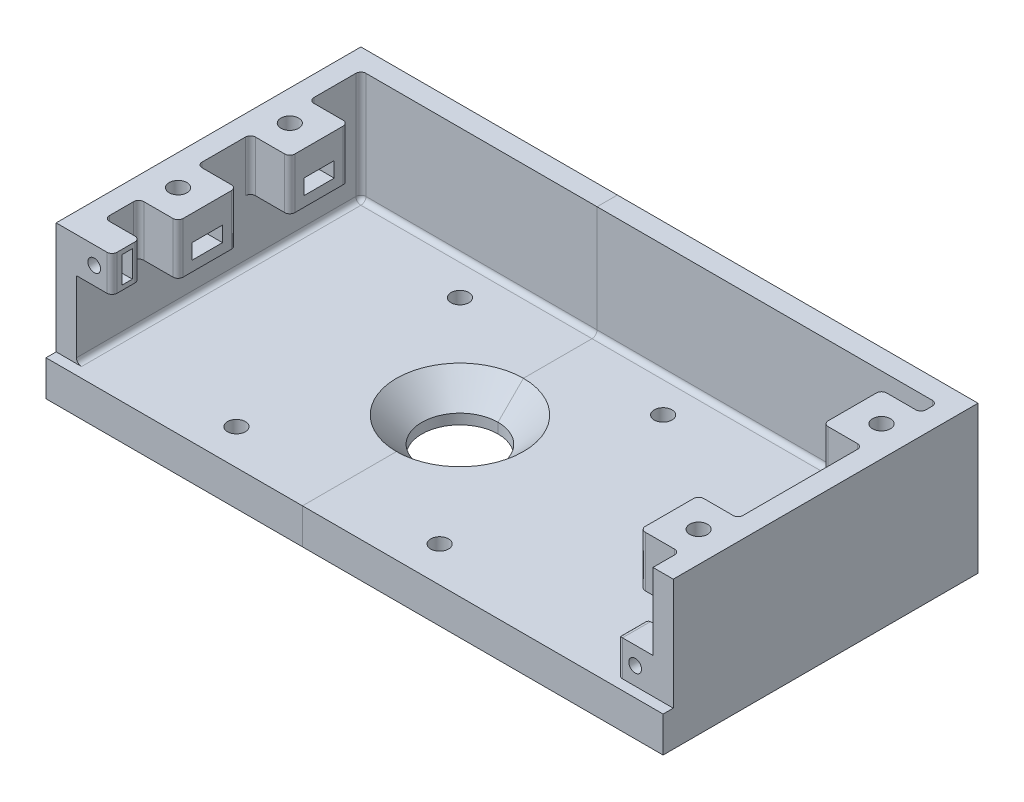
SolidWorks part; units mm, degrees
ref_plane "Front Plane" through (0, 0, 0) normal (0, 0, 1) x (1, 0, 0)
ref_plane "Top Plane" through (0, 0, 0) normal (0, 1, 0) x (1, 0, 0)
ref_plane "Right Plane" through (0, 0, 0) normal (1, 0, 0) x (0, 0, -1)
sketch "Sketch1" plane through (0, 0, 0) normal (0, 1, 0) x (1, 0, 0)
  line L0 (-50.5, 0) -> (71, 0) construction
  line L1 (-50.5, 31) -> (71, 31)
  line L2 (-50.5, 31) -> (-50.5, -31)
  line L3 (-50.5, -31) -> (71, -31)
  line L4 (71, 31) -> (71, -31)
  dimension "D1" = 121.5
  dimension "D2" = 62
  dimension "D3" = 71
extrude "Boss-Extrude1" add sketch "Sketch1" along normal blind 7
hole_wizard "CSK for M10 Flat Head Machine Screw1" positions "Sketch2" profile "Sketch3" countersink size "M10" standard "ANSI Metric" end condition through all
sketch "Sketch2" plane through (0, 7, 0) normal (0, 1, 0) x (1, 0, 0)
  point P0 (0, 0)
sketch "Sketch3" plane through (0, 7, 0) normal (1, 0, 0) x (0, 0, 1)
  line L0 (0, 0) -> (0, 7)
  line L1 (0, 7) -> (7.5, 7)
  line L2 (7.5, 7) -> (7.5, 5)
  line L3 (7.5, 5) -> (12.5, 0)
  line L5 (12.5, 0) -> (0, 0)
  line L6 (-7.5, 5) -> (-12.5, 0) construction
  line L11 (0, -6.35) -> (0, 107.95) construction
  dimension "Thru Hole Dia." = 15
  dimension "Thru Hole Depth" = 7
  dimension "Near C'Sink Dia." = 25
  dimension "Near C'Sink Angle" = 90
sketch "Sketch4" plane through (0, 7, 0) normal (0, 1, 0) x (1, 0, 0)
  line L8 (-50.5, 31) -> (-50.5, -29)
  line L9 (-50.5, 31) -> (-50.5, -31) construction
  line L10 (-50.5, -29) -> (-46.5, -29)
  line L11 (-46.5, -29) -> (-46.5, 27)
  line L12 (-46.5, 27) -> (67, 27)
  line L13 (67, 27) -> (67, -29)
  line L14 (67, -29) -> (71, -29)
  line L15 (71, -31) -> (71, 31) construction
  line L16 (71, -29) -> (71, 31)
  line L17 (71, 31) -> (-50.5, 31)
  line L18 (-50.5, -31) -> (71, -31) construction
  dimension "D1" = 2
  dimension "D2" = 4
  dimension "D3" = 4
extrude "Boss-Extrude2" add sketch "Sketch4" along normal blind 22
sketch "Sketch5" plane through (0, 29, 0) normal (0, 1, 0) x (1, 0, 0)
  line L1 (-50.25, 16.75) -> (-38.75, 16.75)
  line L2 (-50.25, 16.75) -> (-50.25, 5.25)
  line L3 (-50.25, 5.25) -> (-38.75, 5.25)
  line L4 (-38.75, 16.75) -> (-38.75, 5.25)
  line L5 (-50.25, 16.75) -> (-38.75, 5.25) construction
  line L6 (-50.25, 5.25) -> (-38.75, 16.75) construction
  line L7 (-50.25, -5.25) -> (-38.75, -5.25)
  line L8 (-50.25, -5.25) -> (-50.25, -16.75)
  line L9 (-50.25, -16.75) -> (-38.75, -16.75)
  line L10 (-38.75, -5.25) -> (-38.75, -16.75)
  line L11 (-50.25, -5.25) -> (-38.75, -16.75) construction
  line L12 (-50.25, -16.75) -> (-38.75, -5.25) construction
  line L13 (59.25, 23.75) -> (70.75, 23.75)
  line L14 (59.25, 23.75) -> (59.25, 12.25)
  line L15 (59.25, 12.25) -> (70.75, 12.25)
  line L16 (70.75, 23.75) -> (70.75, 12.25)
  line L17 (59.25, 23.75) -> (70.75, 12.25) construction
  line L18 (59.25, 12.25) -> (70.75, 23.75) construction
  line L19 (59.25, -12.25) -> (70.75, -12.25)
  line L20 (59.25, -12.25) -> (59.25, -23.75)
  line L21 (59.25, -23.75) -> (70.75, -23.75)
  line L22 (70.75, -12.25) -> (70.75, -23.75)
  line L23 (59.25, -12.25) -> (70.75, -23.75) construction
  line L24 (59.25, -23.75) -> (70.75, -12.25) construction
  point P0 (-44.5, 11)
  point P6 (-44.5, -11)
  point P12 (65, 18)
  point P18 (65, -18)
  point P24 (0, 0)
  dimension "D1" = 11.5
extrude "Boss-Extrude3" add sketch "Sketch5" against normal blind 10
sketch "Sketch6" plane through (0, 19, 0) normal (0, 1, 0) x (1, 0, 0)
  line L0 (-42.7679, -8) -> (-38.75, -8)
  line L1 (-46.2321, 8) -> (-42.7679, 8)
  line L2 (-42.7679, 8) -> (-41.0359, 11)
  line L3 (-41.0359, 11) -> (-42.7679, 14)
  line L4 (-42.7679, 14) -> (-46.2321, 14)
  line L5 (-46.2321, 14) -> (-47.9641, 11)
  line L6 (-47.9641, 11) -> (-46.2321, 8)
  line L7 (-41.0359, -11) -> (-42.7679, -8)
  line L8 (-42.7679, -8) -> (-46.2321, -8)
  line L9 (-46.2321, -8) -> (-47.9641, -11)
  line L10 (-47.9641, -11) -> (-46.2321, -14)
  line L11 (-46.2321, -14) -> (-42.7679, -14)
  line L12 (-42.7679, -14) -> (-41.0359, -11)
  line L13 (66.7321, 15) -> (68.4641, 18)
  line L14 (68.4641, 18) -> (66.7321, 21)
  line L15 (66.7321, 21) -> (63.2679, 21)
  line L16 (63.2679, 21) -> (61.5359, 18)
  line L17 (61.5359, 18) -> (63.2679, 15)
  line L18 (63.2679, 15) -> (66.7321, 15)
  line L19 (66.7321, -21) -> (68.4641, -18)
  line L20 (68.4641, -18) -> (66.7321, -15)
  line L21 (66.7321, -15) -> (63.2679, -15)
  line L22 (63.2679, -15) -> (61.5359, -18)
  line L23 (61.5359, -18) -> (63.2679, -21)
  line L24 (63.2679, -21) -> (66.7321, -21)
  line L25 (-38.75, -16.75) -> (-38.75, -5.25) construction
  line L26 (-38.75, -8) -> (-38.75, -14)
  line L27 (-38.75, -14) -> (-42.7679, -14)
  line L28 (-42.7679, 14) -> (-38.75, 14)
  line L29 (-38.75, 5.25) -> (-38.75, 16.75) construction
  line L30 (-38.75, 14) -> (-38.75, 8)
  line L31 (-38.75, 8) -> (-42.7679, 8)
  line L32 (63.2679, 21) -> (59.25, 21)
  line L33 (59.25, 23.75) -> (59.25, 12.25) construction
  line L34 (59.25, 21) -> (59.25, 15)
  line L35 (59.25, 15) -> (63.2679, 15)
  line L36 (63.2679, -15) -> (59.25, -15)
  line L37 (59.25, -12.25) -> (59.25, -23.75) construction
  line L38 (59.25, -15) -> (59.25, -21)
  line L39 (59.25, -21) -> (63.2679, -21)
  circle A0 centre (-44.5, 11) radius 3 construction
  circle A1 centre (-44.5, -11) radius 3 construction
  circle A2 centre (65, 18) radius 3 construction
  circle A3 centre (65, -18) radius 3 construction
  point P52 (0, 0)
  dimension "D1" = 6
extrude "Cut-Extrude1" cut sketch "Sketch6" along normal blind 3 from offset 2
sketch "Sketch7" plane through (0, 29, 0) normal (0, 1, 0) x (1, 0, 0)
  circle A0 centre (-44.5, 11) radius 1.75
  circle A1 centre (-44.5, -11) radius 1.75
  circle A2 centre (65, 18) radius 1.75
  circle A3 centre (65, -18) radius 1.75
  point P12 (0, 0)
  dimension "D1" = 3.5
extrude "Cut-Extrude2" cut sketch "Sketch7" against normal up to surface (10 mm away) contours A0 | A1 | A2 | A3 up to face at (63.125, 19, 18)
sketch "Sketch8" plane through (0, 0, 29) normal (0, 0, 1) x (1, 0, 0)
  line L0 (-39.5, 29) -> (-46.5, 22) construction
  line L5 (-46.5, 29) -> (-39.5, 29)
  line L6 (-46.5, 29) -> (-46.5, 22)
  line L7 (-46.5, 22) -> (-39.5, 22)
  line L8 (-39.5, 29) -> (-39.5, 22)
  line L9 (67, 7) -> (60, 7)
  line L10 (67, 7) -> (67, 14)
  line L11 (67, 14) -> (60, 14)
  line L12 (60, 7) -> (60, 14)
  line L19 (60, 14) -> (67, 7) construction
  circle A0 centre (-43, 25.5) radius 1.25
  circle A3 centre (63.5, 10.5) radius 1.25
  point P28 (-41.7077, 26.4256)
  point P29 (0, 0)
  point P30 (-43.25, 25.75)
  dimension "D2" = 2.5
  dimension "D1" = 7
extrude "Boss-Extrude5" add sketch "Sketch8" against normal blind 5.5 contours L12 L9 L10 L11 A3
sketch "Sketch9" plane through (0, 0, 29) normal (0, 0, 1) x (1, 0, 0)
  line L0 (-43, 28.0981) -> (-39.5, 28.0981)
  line L1 (-40.75, 24.201) -> (-40.75, 26.799)
  line L2 (-40.75, 26.799) -> (-43, 28.0981)
  line L3 (-43, 28.0981) -> (-45.25, 26.799)
  line L4 (-45.25, 26.799) -> (-45.25, 24.201)
  line L5 (-45.25, 24.201) -> (-43, 22.9019)
  line L6 (-43, 22.9019) -> (-40.75, 24.201)
  line L7 (65.75, 9.201) -> (65.75, 11.799)
  line L8 (65.75, 11.799) -> (63.5, 13.0981)
  line L9 (63.5, 13.0981) -> (61.25, 11.799)
  line L10 (61.25, 11.799) -> (61.25, 9.201)
  line L11 (61.25, 9.201) -> (63.5, 7.9019)
  line L12 (63.5, 7.9019) -> (65.75, 9.201)
  line L13 (-39.5, 29) -> (-39.5, 22) construction
  line L14 (-39.5, 28.0981) -> (-39.5, 22.9019)
  line L15 (-39.5, 22.9019) -> (-43, 22.9019)
  line L16 (63.5, 13.0981) -> (60, 13.0981)
  line L17 (60, 7) -> (60, 14) construction
  line L18 (60, 13.0981) -> (60, 7.9019)
  line L19 (60, 7.9019) -> (63.5, 7.9019)
  circle A0 centre (-43, 25.5) radius 2.25 construction
  circle A1 centre (63.5, 10.5) radius 2.25 construction
  line M16 (-39.5, 22) -> (-39.5, 29)
  circle M19 centre (-43, 25.5) radius 1.25
  dimension "D1" = 4.5
  dimension "D2" = 4.5
extrude "Cut-Extrude3" cut sketch "Sketch9" against normal blind 2 from offset 2 contours L15 L0 L2 L1 L6 M16 | L5 L6 L1 L2 L3 L4 M19 | L18 L19 L11 L10 L9 L16 | L11 L12 L7 L8 L9 L10 offset against normal yes
sketch "Sketch10" plane through (0, 29, 0) normal (0, 1, 0) x (1, 0, 0)
  line L0 (0, 31) -> (0, -31)
  line L1 (71, 31) -> (-50.5, 31) construction
  line L2 (-50.5, -31) -> (71, -31) construction
sketch "Sketch11" plane through (0, 7, 0) normal (0, 1, 0) x (1, 0, 0)
  line L0 (-46.5, 27) -> (67, 27) construction
  line L1 (-50.5, -31) -> (71, -31) construction
  circle A0 centre (-20, 20) radius 1.75
  circle A1 centre (20, 20) radius 1.75
  circle A2 centre (-20, -24) radius 1.75
  circle A3 centre (20, -24) radius 1.75
  point P8 (0, 0)
  point P9 (0, 0)
  point P10 (0, 0)
  point P11 (0, 0)
  point P12 (0, 0)
  point P13 (0, 0)
  point P14 (0, 0)
  point P16 (-15.6991, 19.7968)
  dimension "D1" = 3.5
  dimension "D2" = 20
  dimension "D3" = 20
  dimension "D4" = 7
  dimension "D5" = 7
extrude "Cut-Extrude4" cut sketch "Sketch11" against normal through all
fillet "Fillet1" radius 1 28 edges at (60, 14, 26.25) (60, 10.5, 29) (60, 10.5, 23.5) (67, 10.5, 23.5) (59.25, 24, 12.25) (59.25, 24, 23.75) (67, 24, 23.75) (67, 24, 12.25) (67, 24, -12.25) (67, 24, -23.75) (67, 18, -27) (59.25, 24, -23.75) (59.25, 24, -12.25) (-46.5, 18, -27) (-38.75, 24, -5.25) (-38.75, 24, -16.75) (-46.5, 24, -16.75) (-46.5, 24, -5.25) (-46.5, 25.5, 23.5) (-38.75, 24, 16.75) (-38.75, 24, 5.25) (-46.5, 24, 5.25) (-46.5, 24, 16.75) (-39.5, 25.5, 23.5) (-39.5, 25.5, 29) (67, 7, -1.75) (-46.5, 7, 1) (10.25, 7, -27)
split "Split1" trim tools "Sketch10" bodies to split 109 resulting bodies 110 111
equation "\"D3@Sketch4\"=\"D2@Sketch4\""
